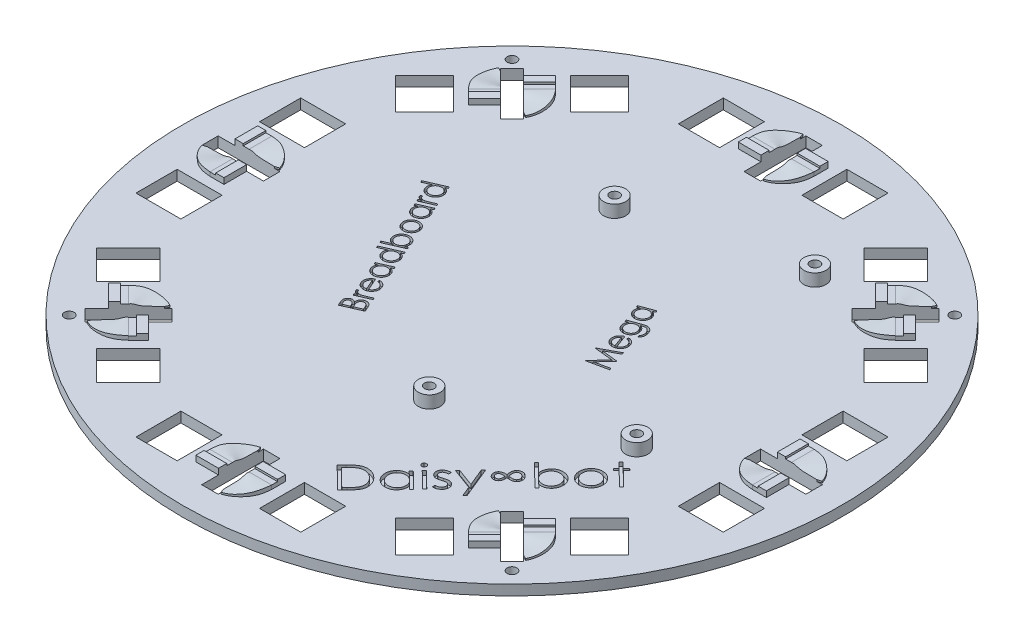
SolidWorks part; units mm, degrees
ref_plane "Front" through (0, 0, 0) normal (0, 0, 1) x (1, 0, 0)
ref_plane "Top" through (0, 0, 0) normal (0, 1, 0) x (1, 0, 0)
ref_plane "Right" through (0, 0, 0) normal (1, 0, 0) x (0, 0, -1)
sketch "Sketch1" plane through (0, 0, 0) normal (0, 1, 0) x (1, 0, 0)
  circle A0 centre (0, 0) radius 101.6
  dimension "D1" = 203.2
extrude "Boss-Extrude1" add sketch "Sketch1" along normal blind 3.175 contours A0
sketch "Sketch2" plane through (0, 3.175, 0) normal (0, 1, 0) x (1, 0, 0)
  line L1 (-2.54, -93.1333) -> (2.54, -93.1333)
  line L2 (-2.54, -93.1333) -> (-2.54, -74.0833)
  line L3 (-2.54, -74.0833) -> (2.54, -74.0833)
  line L4 (2.54, -93.1333) -> (2.54, -74.0833)
  point P4 (0, -74.0833)
  dimension "D1" = 5.08
  dimension "D2" = 19.05
  dimension "D3" = 93.1333
extrude "Cut-Extrude1" cut sketch "Sketch2" against normal up to next and the other way through all contours L1 L4 L3 L2
sketch "Sketch4" plane through (0, 3.175, 0) normal (0, 1, 0) x (1, 0, 0)
  line L0 (0, -83.6083) -> (-2.9434, -74.5495) construction
  line L1 (-2.9434, -74.5495) -> (0, -83.6083) construction
  line L2 (0, -83.6083) -> (-5.5987, -75.9024) construction
  line L3 (0, -83.6083) -> (-7.7059, -78.0097) construction
  line L4 (0, -83.6083) -> (-9.0588, -80.6649) construction
  line L5 (0, -83.6083) -> (-9.525, -83.6083) construction
  line L9 (2.54, -74.0833) -> (-2.54, -74.0833) construction
  line L10 (2.54, -74.0833) -> (2.54, -93.1333) construction
  line L11 (-2.54, -74.0833) -> (-2.54, -93.1333) construction
  line L12 (2.54, -93.1333) -> (-2.54, -93.1333) construction
  circle A0 centre (0, -83.6083) radius 9.525 construction
  point P16 (0, -74.0833)
  point P19 (2.54, -83.6083)
  dimension "D1" = 18
  dimension "D2" = 18
  dimension "D3" = 18
  dimension "D4" = 18
  dimension "D5" = 18
ref_plane "Plane1" through (-24.5719, 0, 7.9839) normal (0.9511, 0, -0.309) x (-0.309, 0, -0.9511)
ref_plane "Plane2" through (-39.7581, 0, 28.886) normal (0.809, 0, -0.5878) x (-0.5878, 0, -0.809)
ref_plane "Plane3" through (-39.7581, 0, 54.7224) normal (0.5878, 0, -0.809) x (-0.809, 0, -0.5878)
ref_plane "Plane4" through (-24.5719, 0, 75.6244) normal (0.309, 0, -0.9511) x (-0.9511, 0, -0.309)
ref_plane "Plane5" through (0, 0, 83.6083) normal (0, 0, -1) x (-1, 0, 0)
sketch "Sketch5" plane through (-24.5719, 0, 7.9839) normal (0.9511, 0, -0.309) x (-0.309, 0, -0.9511)
  line L0 (-69.6725, 3.175) -> (-87.7902, 3.175) construction
  line L1 (-71.2966, 3.175) -> (-69.9913, 3.175)
  line L2 (-71.2966, 3.175) -> (-71.2966, 3.683)
  line L3 (-71.2966, 3.683) -> (-69.9913, 3.683)
  line L4 (-69.9913, 3.175) -> (-69.9913, 3.683)
  dimension "D2" = 0.508
sketch "Sketch6" plane through (-39.7581, 0, 28.886) normal (0.809, 0, -0.5878) x (-0.5878, 0, -0.809)
  line L0 (-58.4417, 3.175) -> (-73.8535, 3.175) construction
  line L1 (-63.3193, 3.175) -> (-58.1156, 3.175)
  line L2 (-63.3193, 3.175) -> (-63.3193, 3.775)
  line L3 (-63.3193, 3.775) -> (-58.1156, 3.775)
  line L4 (-58.1156, 3.175) -> (-58.1156, 3.775)
  dimension "D2" = 0.6
sketch "Sketch7" plane through (-39.7581, 0, 54.7224) normal (0.5878, 0, -0.809) x (-0.809, 0, -0.5878)
  line L0 (-41.4902, 3.175) -> (-52.6875, 3.175) construction
  line L1 (-46.0041, 3.175) -> (-39.6187, 3.175)
  line L2 (-46.0041, 3.175) -> (-46.0041, 4.075)
  line L3 (-46.0041, 4.075) -> (-39.6187, 4.075)
  line L4 (-39.6187, 3.175) -> (-39.6187, 4.075)
  dimension "D2" = 0.9
sketch "Sketch10" plane through (-24.5719, 0, 75.6244) normal (0.309, 0, -0.9511) x (-0.9511, 0, -0.309)
  line L0 (-25.8364, 3.175) -> (-16.7776, 3.175) construction
  line L1 (-23.1657, 3.175) -> (-16.3114, 3.175)
  line L2 (-23.1657, 3.175) -> (-23.1657, 4.375)
  line L3 (-23.1657, 4.375) -> (-16.3114, 4.375)
  line L4 (-16.3114, 3.175) -> (-16.3114, 4.375)
  dimension "D3" = 1.2
sketch "Sketch11" plane through (0, 0, 83.6083) normal (0, 0, -1) x (-1, 0, 0)
  line L0 (0, 3.175) -> (9.525, 3.175) construction
  line L1 (2.54, 3.175) -> (9.525, 3.175)
  line L2 (2.54, 3.175) -> (2.54, 4.375)
  line L3 (2.54, 4.375) -> (9.525, 4.375)
  line L4 (9.525, 3.175) -> (9.525, 4.375)
  dimension "D3" = 1.2
loft "Loft1" add profiles "Sketch5", "Sketch6", "Sketch7", "Sketch10", "Sketch11" connector at (-2.54, 3.683, 75.791) connector at (-2.54, 3.775, 80.1123) connector at (-2.54, 4.075, 81.7629) connector at (-2.54, 4.375, 82.783) connector at (-2.54, 4.375, 83.6083)
sketch "Sketch13" plane through (-104.9799, 0, 83.6083) normal (0, 0, -1) x (-1, 0, 0)
  line L6 (-95.4549, 3.175) -> (-102.4399, 3.175)
  line L7 (-95.4549, 3.175) -> (-95.4549, 4.375)
  line L8 (-95.4549, 4.375) -> (-102.4399, 4.375)
  line L9 (-102.4399, 3.175) -> (-102.4399, 4.375)
extrude "Boss-Extrude4" add sketch "Sketch13" against normal blind 1.7907
sketch "Sketch25" plane through (0, 0, 85.399) normal (0, 0, 1) x (1, 0, 0)
  line L0 (-9.525, 4.375) -> (-2.54, 4.375) construction
  line L1 (-9.525, 3.175) -> (-2.54, 3.175)
  line L2 (-9.525, 3.175) -> (-9.525, 4.975)
  line L3 (-9.525, 4.975) -> (-2.54, 4.975)
  line L4 (-2.54, 3.175) -> (-2.54, 4.975)
  dimension "D1" = 0.6
extrude "Boss-Extrude5" add sketch "Sketch25" along normal blind 2.54
sketch "Sketch14" plane through (-2.54, 0, 0) normal (1, 0, 0) x (0, 0, -1)
  line L0 (-83.6083, 3.175) -> (-83.6083, 0) construction
  line L1 (-74.0833, 0) -> (-93.1333, 0) construction
ref_plane "Plane6" through (0, 0, 0) normal (1, 0, 0) x (0, 0, -1)
sketch "Sketch15" plane through (0, 0, 0) normal (1, 0, 0) x (0, 0, -1)
  line L0 (-83.6083, 0) -> (-83.6083, 3.175) construction
pattern_circular "CirPattern1" count 2 over 360 about axis through (0, 0, 83.6083) along (0, 1, 0) of "Loft1", "Boss-Extrude5", "Boss-Extrude4" reverse direction yes
ref_axis "Axis1" through (0, 50, 0) along (0, -1, 0)
pattern_circular "CirPattern5" count 8 over 360 about axis through (0, 50, 0) along (0, -1, 0) of "CirPattern1", "Cut-Extrude1"
sketch "Sketch18" plane through (0, 3.175, 0) normal (0, 1, 0) x (1, 0, 0)
  line L0 (-12.3739, 44.0137) -> (36.5149, 57.7582) construction
  line L1 (-12.3739, 44.0137) -> (9.9679, -35.4555) construction
  line L2 (36.5149, 57.7582) -> (36.8586, 56.5356) construction
  line L3 (54.6967, -16.2402) -> (8.2378, -29.3015) construction
  line L4 (0, -101.6) -> (0, 101.6) construction
  line L5 (0, -1.7463) -> (0, 1.7463) construction
  line L6 (-101.6, 0) -> (101.6, 0) construction
  line L7 (36.8586, 56.5356) -> (54.6967, -16.2402) construction
  circle A0 centre (-12.3739, 44.0137) radius 3.405
  circle A1 centre (9.9679, -35.4555) radius 3.405
  circle A2 centre (54.6967, -16.2402) radius 3.405
  circle A3 centre (36.8586, 56.5356) radius 3.405
  circle A4 centre (9.9679, -35.4555) radius 1.5
  circle A5 centre (-12.3739, 44.0137) radius 1.5
  circle A6 centre (36.8586, 56.5356) radius 1.5
  circle A7 centre (54.6967, -16.2402) radius 1.5
  circle A8 centre (0, 0) radius 101.6 construction
  dimension "D7" = 1.905
  dimension "D8" = 3
  dimension "D9" = 1.27
  dimension "D1" = 82.55
  dimension "D2" = 74.93
  dimension "D3" = 50.8
  dimension "D4" = 15.703
  dimension "D5" = 36.83
  dimension "D10" = 48.26
sketch "Sketch19" plane through (0, 3.175, 0) normal (0, 1, 0) x (1, 0, 0)
  line L0 (-68.2499, -68.2499) -> (0, 0) construction
  line L1 (0, -101.6) -> (0, 101.6) construction
  circle A1 centre (-68.2499, -68.2499) radius 1.5
  circle A4 centre (0, 0) radius 101.6 construction
  dimension "D4" = 3
  dimension "D6" = 96.52
  dimension "D5" = 45
extrude "Cut-Extrude2" cut sketch "Sketch19" against normal through all
pattern_circular "CirPattern7" count 4 over 360 about axis through (0, 50, 0) along (0, -1, 0) of "Cut-Extrude2"
extrude "Boss-Extrude3" add sketch "Sketch18" along normal blind 3.81
sketch "Sketch23" plane through (0, 3.175, 0) normal (0, 1, 0) x (1, 0, 0)
  line L9 (-2.54, -87.939) -> (-2.54, -93.1333) construction
  line L10 (-25.4, -76.6805) -> (-12.7, -76.6805)
  line L11 (-25.4, -76.6805) -> (-25.4, -90.5362)
  line L16 (-25.4, -90.5362) -> (-12.7, -90.5362)
  line L17 (-12.7, -76.6805) -> (-12.7, -90.5362)
  line L19 (2.54, -74.0833) -> (2.54, -79.2776) construction
  line L20 (0, -50) -> (0, 50) construction
  line L21 (12.7, -76.6805) -> (12.7, -90.5362)
  line L22 (25.4, -90.5362) -> (12.7, -90.5362)
  line L23 (25.4, -76.6805) -> (25.4, -90.5362)
  line L24 (25.4, -76.6805) -> (12.7, -76.6805)
  point P8 (-2.54, -90.5362)
  point P9 (2.54, -76.6805)
  dimension "D1" = 12.7
  dimension "D2" = 10.16
extrude "Cut-Extrude6" cut sketch "Sketch23" against normal through all
pattern_circular "CirPattern8" count 8 over 360 about axis through (0, 50, 0) along (0, -1, 0) of "Cut-Extrude6"
sketch "Sketch17" plane through (0, 3.175, 0) normal (0, 1, 0) x (1, 0, 0)
  line L0 (19.0413, -74.398) -> (63.1398, -28.708) construction
  dimension "D2" = 74.398
  dimension "D1" = 63.5
  dimension "D3" = 69.3598
  dimension "D4" = 76.796
sketch "Sketch16" plane through (0, 3.175, 0) normal (0, 1, 0) x (1, 0, 0)
  line L0 (19.0413, -74.398) -> (63.1398, -28.708) construction
  line L1 (25.4, -76.6805) -> (12.7, -76.6805) construction
  text T0 "Daisy∞bot\r\n" font "Century Gothic" height in points 36
extrude "Cut-Extrude4" cut sketch "Sketch16" against normal blind 1.27
sketch "Sketch22" plane through (0, 3.175, 0) normal (0, 1, 0) x (1, 0, 0)
  line L0 (-44.1287, 25.1735) -> (-20.5694, -28.6741) construction
  text T0 "Breadboard"
extrude "Cut-Extrude5" cut sketch "Sketch22" against normal blind 1.27
sketch "Sketch24" plane through (0, 3.175, 0) normal (0, 1, 0) x (1, 0, 0)
  line L0 (29.8571, 0) -> (21.0896, 23.8389) construction
  text T0 "Mega"
  dimension "D1" = 28.022
  dimension "D2" = 25.4
  dimension "D3" = 29.8571
extrude "Cut-Extrude7" cut sketch "Sketch24" against normal blind 1.27
